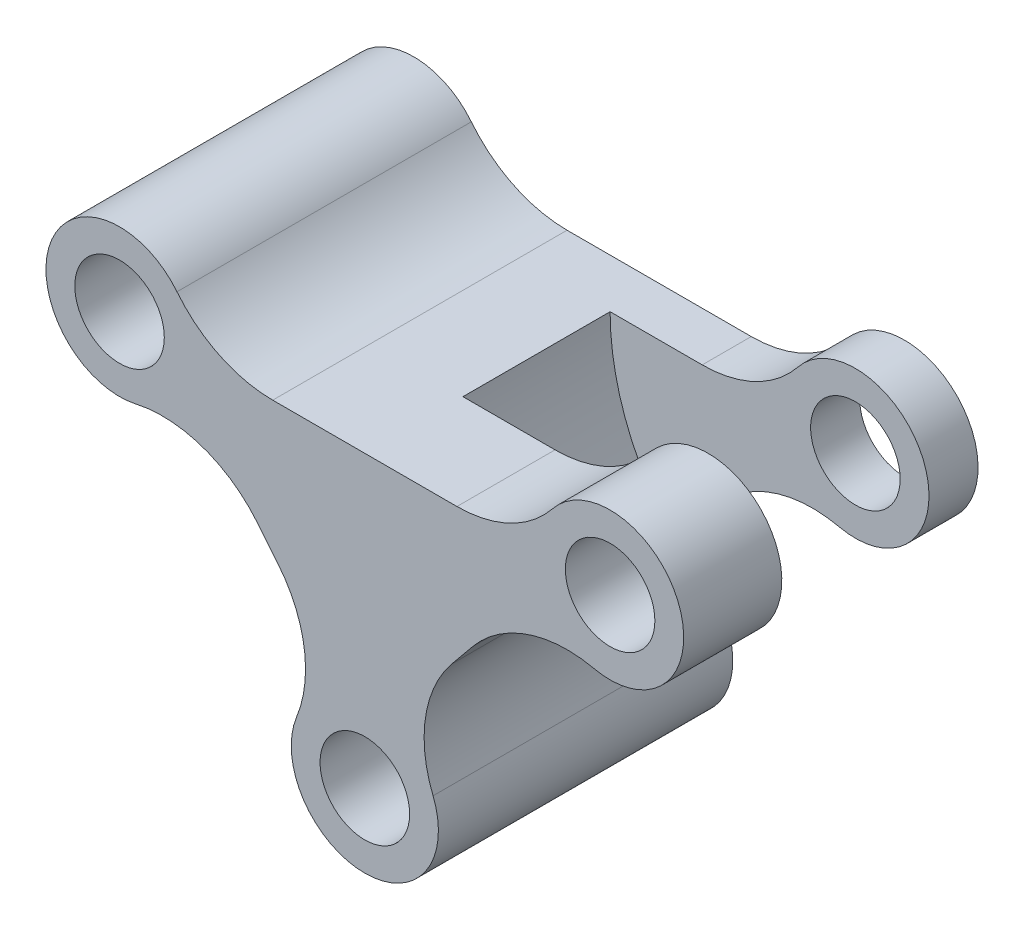
SolidWorks part; units mm, degrees
ref_plane "Plan de face" through (0, 0, 0) normal (0, 0, 1) x (1, 0, 0)
ref_plane "Plan de dessus" through (0, 0, 0) normal (0, 1, 0) x (1, 0, 0)
ref_plane "Plan de droite" through (0, 0, 0) normal (1, 0, 0) x (0, 0, -1)
sketch "Esquisse2" plane through (0, 0, 0) normal (0, 0, 1) x (1, 0, 0)
  line L0 (-8.175, 5) -> (8.175, 5)
  line L1 (8.175, 5) -> (0, -5)
  line L2 (0, -5) -> (-8.175, 5)
  line L3 (0, 0) -> (-8.175, 5) construction
  line L4 (0, 0) -> (8.175, 5) construction
  circle A0 centre (-10, 5) radius 3
  circle A1 centre (-10, 5) radius 1.825
  circle A2 centre (10, 5) radius 3
  circle A3 centre (10, 5) radius 1.825
  circle A4 centre (0, -6.825) radius 3
  circle A5 centre (0, -6.825) radius 1.825
  dimension "D2" = 3.65
  dimension "D3" = 6
  dimension "D1" = 5
  dimension "D4" = 5
  dimension "D5" = 10
extrude "Boss.-Extru.1" add sketch "Esquisse2" along normal blind 12 contours A4 L1 A2 L0 A0 L2 | L1 A5 L2 A4 | L1 A4 L2 | A3 | A1
ref_plane "Plan1" through (0, 0, 2) normal (0, 0, 1) x (1, 0, 0)
sketch "Esquisse3" plane through (0, 0, 2) normal (0, 0, 1) x (1, 0, 0)
  circle A0 centre (10, 5) radius 10
  dimension "D1" = 20
extrude "Enlèv. mat.-Extru.1" cut sketch "Esquisse3" along normal blind 6
fillet "Congé1" radius 5 6 edges at (-7, 5, 6) (-7.2311, 3.8454, 6) (-0.8581, -3.9503, 6) (7.2311, 3.8454, 10) (7, 5, 10) (0.8581, -3.9503, 6)
fillet "Fillet1" radius 5 2 edges at (7, 5, 1) (7.2311, 3.8454, 1)
